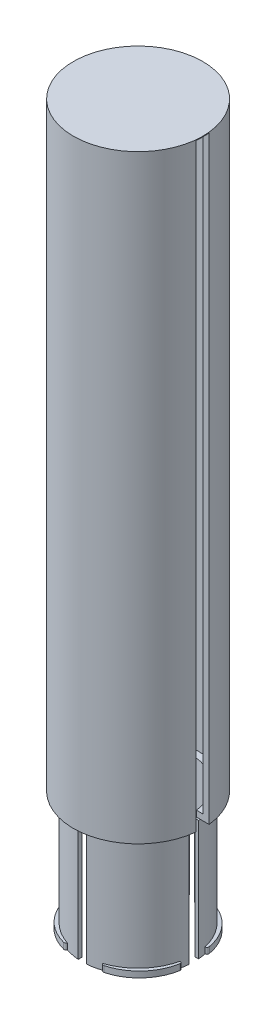
SolidWorks part; units mm, degrees
ref_plane "Front Plane" through (0, 0, 0) normal (0, 0, 1) x (1, 0, 0)
ref_plane "Top Plane" through (0, 0, 0) normal (0, 1, 0) x (1, 0, 0)
ref_plane "Right Plane" through (0, 0, 0) normal (1, 0, 0) x (0, 0, -1)
sketch "Sketch1" plane through (0, 0, 0) normal (0, 1, 0) x (1, 0, 0)
  line L5 (15.2664, 15.2664) -> (-15.2664, -15.2664) construction
  line L6 (15.2664, -15.2664) -> (-15.2664, 15.2664) construction
  circle A0 centre (0, 0) radius 21.59
  point P0 (0, 0)
  dimension "D1" = 43.18
extrude "Boss-Extrude1" add sketch "Sketch1" along normal blind 200
shell "Shell1" thickness 2
sketch "Sketch2" plane through (0, 0, 0) normal (1, 0, 0) x (0, 0, -1)
  line L0 (0, 19.558) -> (0, -19.558) construction
  line L2 (2.214, 104.2698) -> (2.214, 0)
  line L3 (2.214, 0) -> (-2.214, 0)
  line L4 (-2.214, 104.2698) -> (-2.214, 0)
  line L5 (2.214, 104.2698) -> (-2.214, 0) construction
  line L6 (2.214, 0) -> (-2.214, 104.2698) construction
  line L7 (19.558, 0) -> (-19.558, 0) construction
  line L10 (-2.214, 104.2698) -> (-2.214, 199.7944)
  line L11 (-2.214, 199.7944) -> (2.214, 199.7944)
  line L12 (2.214, 104.2698) -> (2.214, 199.7944)
  point P0 (0, 52.1349)
extrude "Cut-Extrude1" cut sketch "Sketch2" against normal mid plane 10 from offset 20
sketch "Sketch4" plane through (0, 0, 0) normal (0, -1, 0) x (1, 0, 0)
  circle A0 centre (0, 0) radius 18.651
extrude "Boss-Extrude2" add sketch "Sketch4" along normal blind 40
sketch "Sketch7" plane through (0, -40, 0) normal (0, -1, 0) x (-1, 0, 0)
  circle A0 centre (0, 0) radius 17.4097
extrude "Cut-Extrude4" cut sketch "Sketch7" against normal blind 62
sketch "Sketch8" plane through (0, 0, 0) normal (0, 1, 0) x (1, 0, 0)
  line L0 (0, -19.558) -> (0, 19.558) construction
  line L1 (-1.3929, 23.0464) -> (1.3929, 23.0464)
  line L2 (-1.3929, 23.0464) -> (-1.3929, 17.1698)
  line L3 (-1.3929, 17.1698) -> (1.3929, 17.1698)
  line L4 (1.3929, 23.0464) -> (1.3929, 17.1698)
  line L5 (-1.3929, 23.0464) -> (1.3929, 17.1698) construction
  line L6 (-1.3929, 17.1698) -> (1.3929, 23.0464) construction
  line L7 (14.2708, 1.6027) -> (23.1489, 1.6027)
  line L8 (14.2708, 1.6027) -> (14.2708, -1.6047)
  line L9 (14.2708, -1.6047) -> (23.1489, -1.6047)
  line L10 (23.1489, 1.6027) -> (23.1489, -1.6047)
  line L11 (14.2708, 1.6027) -> (23.1489, -1.6047) construction
  line L12 (14.2708, -1.6047) -> (23.1489, 1.6027) construction
  line L13 (-1.3657, -14.1994) -> (1.3929, -14.1994)
  line L14 (-1.3657, -14.1994) -> (-1.3657, -22.705)
  line L15 (-1.3657, -22.705) -> (1.3929, -22.705)
  line L16 (1.3929, -14.1994) -> (1.3929, -22.705)
  line L17 (-1.3657, -14.1994) -> (1.3929, -22.705) construction
  line L18 (-1.3657, -22.705) -> (1.3929, -14.1994) construction
  line L19 (-14.2708, 1.6027) -> (-23.1489, 1.6027)
  line L20 (-23.1489, 1.6027) -> (-23.1489, -1.6047)
  line L21 (-14.2708, -1.6047) -> (-23.1489, -1.6047)
  line L22 (-14.2708, 1.6027) -> (-14.2708, -1.6047)
  point P0 (0, 20.1081)
  point P5 (18.7098, -0.001)
  point P10 (0.0136, -18.4522)
  point P21 (0, 0)
  point P22 (0, 18.7444)
  point P23 (0, 0)
  point P24 (0, 0)
  point P25 (-1.3657, -20.4516)
  point P26 (0, 0)
  point P27 (20.2126, -1.6047)
extrude "Cut-Extrude5" cut sketch "Sketch8" against normal through all
sketch "Sketch9" plane through (0, -40, 0) normal (0, -1, 0) x (1, 0, 0)
  line L0 (23.749, 0) -> (-23.749, 0) construction
  line L2 (0, -23.749) -> (0, 23.749) construction
  arc A0 (6.5311, 17.4702) -> (18.1838, 4.8127) centre (2.5628, 2.1243) cw construction
  arc A1 (18.8328, 4.9244) -> (6.6959, 18.1077) centre (2.5628, 2.1243) ccw
  arc A2 (17.5348, 4.701) -> (6.3662, 16.8326) centre (2.5628, 2.1243) ccw
  arc A3 (17.5348, 4.701) -> (18.8328, 4.9244) centre (18.1838, 4.8127) ccw
  arc A4 (6.6959, 18.1077) -> (6.3662, 16.8326) centre (6.5311, 17.4702) ccw
  arc A5 (6.5311, -17.4702) -> (18.1838, -4.8127) centre (2.5628, -2.1243) ccw construction
  arc A6 (18.8328, -4.9244) -> (6.6959, -18.1077) centre (2.5628, -2.1243) cw
  arc A7 (17.5348, -4.701) -> (6.3662, -16.8326) centre (2.5628, -2.1243) cw
  arc A8 (17.5348, -4.701) -> (18.8328, -4.9244) centre (18.1838, -4.8127) cw
  arc A9 (6.6959, -18.1077) -> (6.3662, -16.8326) centre (6.5311, -17.4702) cw
  arc A10 (-6.5311, -17.4702) -> (-18.1838, -4.8127) centre (-2.5628, -2.1243) cw construction
  arc A11 (-18.8328, -4.9244) -> (-6.6959, -18.1077) centre (-2.5628, -2.1243) ccw
  arc A12 (-17.5348, -4.701) -> (-6.3662, -16.8326) centre (-2.5628, -2.1243) ccw
  arc A13 (-17.5348, -4.701) -> (-18.8328, -4.9244) centre (-18.1838, -4.8127) ccw
  arc A14 (-6.6959, -18.1077) -> (-6.3662, -16.8326) centre (-6.5311, -17.4702) ccw
  arc A15 (-6.5311, 17.4702) -> (-18.1838, 4.8127) centre (-2.5628, 2.1243) ccw construction
  arc A16 (-18.8328, 4.9244) -> (-6.6959, 18.1077) centre (-2.5628, 2.1243) cw
  arc A17 (-17.5348, 4.701) -> (-6.3662, 16.8326) centre (-2.5628, 2.1243) cw
  arc A18 (-17.5348, 4.701) -> (-18.8328, 4.9244) centre (-18.1838, 4.8127) cw
  arc A19 (-6.6959, 18.1077) -> (-6.3662, 16.8326) centre (-6.5311, 17.4702) cw
  arc A20 (18.5192, 2.214) -> (1.3929, 18.599) centre (0, 0) ccw construction
  point P3 (14.2242, 12.86)
  point P15 (14.2242, -12.86)
  point P23 (-14.2242, -12.86)
  point P31 (-14.2242, 12.86)
  point P36 (-6.2301, -17.5797)
  point P40 (-6.5855, 17.383)
  point P41 (-6.3662, 17.4702)
extrude "Boss-Extrude4" add sketch "Sketch9" against normal blind 2
